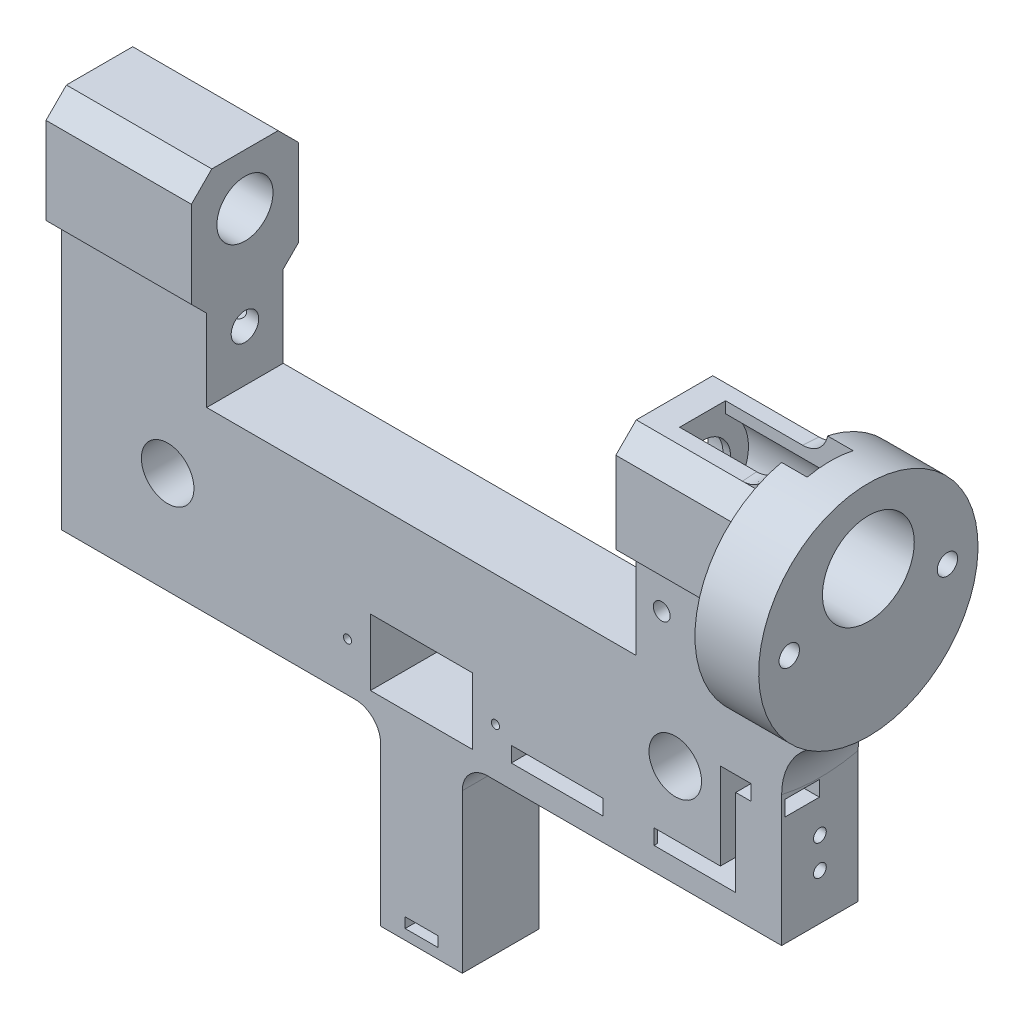
SolidWorks part; units mm, degrees
ref_plane "Front Plane" through (0, 0, 0) normal (0, 0, 1) x (1, 0, 0)
ref_plane "Top Plane" through (0, 0, 0) normal (0, 1, 0) x (1, 0, 0)
ref_plane "Right Plane" through (0, 0, 0) normal (1, 0, 0) x (0, 0, -1)
sketch "Croquis1" plane through (0, 0, 0) normal (0, 1, 0) x (1, 0, 0)
  line L1 (-20, -7.5) -> (20, -7.5)
  line L2 (-20, -7.5) -> (-20, 7.5)
  line L3 (-20, 7.5) -> (20, 7.5)
  line L4 (20, -7.5) -> (20, 7.5)
  line L5 (-20, -7.5) -> (20, 7.5) construction
  line L6 (-20, 7.5) -> (20, -7.5) construction
  point P0 (0, 0)
  dimension "D1" = 40
  dimension "D2" = 15
extrude "Saliente-Extruir1" add sketch "Croquis1" along normal blind 75
sketch "Croquis4" plane through (20, 0, 0) normal (1, 0, 0) x (0, 0, -1)
  line L5 (0, 75) -> (0, 46.5638) construction
  line L6 (-7.5, 75) -> (7.5, 75) construction
  line L11 (0, 58) -> (16.3781, 58) construction
  circle A0 centre (0, 58) radius 21.5
  circle A1 centre (0, 58) radius 15.5 construction
  circle A5 centre (-15.5, 58) radius 2
  circle A6 centre (15.5, 58) radius 2
  dimension "D3" = 43
  dimension "D5" = 31
  dimension "D1" = 4
  dimension "D2" = 4
  dimension "D4" = 17
extrude "Saliente-Extruir2" add sketch "Croquis4" against normal blind 3
sketch "Croquis7" plane through (0, 0, 7.5) normal (0, 0, 1) x (1, 0, 0)
  line L0 (20, 0) -> (-121.2, 0) construction
  line L1 (-121.2, 0) -> (-121.2, 75)
  line L2 (-121.2, 75) -> (-92.7, 75)
  line L3 (-92.7, 75) -> (-92.7, 35)
  line L4 (-92.7, 35) -> (-81.2, 35)
  line L5 (-81.2, 35) -> (-81.2, 0)
  line L6 (-81.2, 0) -> (-121.2, 0)
  line L7 (-81.2, 20) -> (-20, 20)
  line L8 (-81.2, 0) -> (-20, 0)
  line L9 (-59.6, 0) -> (-59.6, -30)
  line L10 (-41.6, 0) -> (-41.6, -30)
  line L11 (-59.6, -30) -> (-41.6, -30)
  line L12 (-20, 75) -> (-20, 0) construction
  line L13 (-50.6, 0) -> (-52.95, 0) construction
  line L14 (-99.5, 0) -> (-99.5, 20.0495) construction
  line L15 (20, 0) -> (-121.2, 0) construction
  line L16 (-50.6, 20) -> (-50.6, -48.6966) construction
  line M17 (-20, 75) -> (-20, 0)
  dimension "D1" = 141.2
  dimension "D2" = 75
  dimension "D3" = 28.5
  dimension "D4" = 11.5
  dimension "D5" = 35
  dimension "D6" = 9
  dimension "D7" = 30
  dimension "D8" = 68.6966
  dimension "D9" = 30
  dimension "D10" = 20
  dimension "D11" = 2.35
  dimension "D12" = 99.5
  dimension "D13" = 9
extrude "Saliente-Extruir3" add sketch "Croquis7" against normal blind 15 contours L9 L11 L10 L8 | L5 L8 L7 M17 | L6 L5 L4 L3 L2 L1 region at (-103.7807, 34.3307, 7.5) region at (-50.6, 10, 7.5) region at (-50.6, -15, 7.5)
sketch "Croquis8" plane through (0, 0, 7.5) normal (0, 0, 1) x (1, 0, 0)
  line L0 (-50.6, -30) -> (-50.6, 95.9893) construction
  line L1 (-59.6, -30) -> (-41.6, -30) construction
  line L2 (-41.6, 0) -> (20, 0) construction
  circle A6 centre (-0.85, 20) radius 2.7
  circle A7 centre (-100.35, 20) radius 2.7
  dimension "D1" = 5.4
  dimension "D2" = 20
  dimension "D3" = 49.75
extrude "Cortar-Extruir5" cut sketch "Croquis8" against normal blind 20
sketch "Croquis6" plane through (0, 0, 7.5) normal (0, 0, 1) x (1, 0, 0)
  line L0 (0, 75) -> (-8.5, 75) construction
  line L1 (-20, 75) -> (17, 75) construction
  line L2 (-20, 75) -> (-8.5, 75)
  line L3 (-8.5, 75) -> (-8.5, 35)
  line L4 (-8.5, 35) -> (-20, 35)
  line L5 (-20, 75) -> (-20, 20) construction
  line L6 (-20, 35) -> (-20, 75)
  line L7 (0, 25) -> (0, 75) construction
  dimension "D1" = 8.5
  dimension "D2" = 40
extrude "Cortar-Extruir4" cut sketch "Croquis6" against normal blind 40
extrude "Saliente-Extruir5" add sketch "Croquis4<2>" along normal blind 9.5
sketch "Croquis4<2>" plane through (20, 0, 0) normal (1, 0, 0) x (0, 0, -1) same geometry as "Croquis4"
sketch "Croquis3" plane through (-20, 0, 0) normal (-1, 0, 0) x (0, 0, 1)
  line L1 (-7.5, 0) -> (7.5, 0) construction
  line L2 (-7.5, 75) -> (7.5, 75) construction
  circle A0 centre (0, 65) radius 5.5
  circle A1 centre (0, 45) radius 2.7
  point P9 (0, 0)
  dimension "D1" = 11
  dimension "D3" = 5.4
  dimension "D2" = 10
  dimension "D4" = 20
  dimension "D5" = 45
extrude "Cortar-Extruir2" cut sketch "Croquis3" against normal mid plane 290
sketch "Croquis10" plane through (20, 0, 0) normal (1, 0, 0) x (0, 0, -1)
  circle A1 centre (0, 65) radius 7
  dimension "D2" = 14
extrude "Cortar-Extruir7" cut sketch "Croquis10" against normal blind 23
sketch "Croquis11" plane through (-121.2, 0, 0) normal (-1, 0, 0) x (0, 0, 1)
  circle A1 centre (0, 65) radius 6.6
  circle M2 centre (0, 65) radius 5.5
  dimension "D2" = 13.2
extrude "Cortar-Extruir8" cut sketch "Croquis11" against normal blind 6 contours A1 M2 region at (-121.2, 65, -6.4133)
sketch "Croquis13" plane through (-8.5, 0, 0) normal (-1, 0, 0) x (0, 0, 1)
  circle A0 centre (0, 65) radius 6.6
  dimension "D1" = 13.2
extrude "Cortar-Extruir10" cut sketch "Croquis13" against normal blind 4
sketch "Croquis17" plane through (0, 0, -7.5) normal (0, 0, -1) x (-1, 0, 0)
  line L0 (-17, 75) -> (8.5, 75) construction
  line L1 (8.5, 35) -> (8.5, 75) construction
  circle A0 centre (-3, 34) radius 0.8
  circle A1 centre (-3, 43.38) radius 0.8
  dimension "D4" = 1.6
  dimension "D5" = 1.6
  dimension "D1" = 9.38
  dimension "D2" = 41
  dimension "D3" = 11.5
extrude "Cortar-Extruir13" cut sketch "Croquis17" against normal blind 4 contours A0 | A1 region at (3, 34, -7.5) region at (3, 43.38, -7.5)
sketch "Croquis18" plane through (0, 0, -7.5) normal (0, 0, -1) x (-1, 0, 0)
  line L0 (20, 35) -> (81.2, 35)
  line L1 (81.2, 35) -> (81.2, 20)
  line L2 (81.2, 20) -> (20, 20)
  line L3 (20, 20) -> (20, 35)
extrude "Saliente-Extruir4" add sketch "Croquis18" against normal blind 15
sketch "Croquis19" plane through (0, 0, -7.5) normal (0, 0, -1) x (-1, 0, 0)
  line L0 (92.7, 35) -> (8.5, 35) construction
  circle A0 centre (28.5, 27) radius 0.8
  circle A1 centre (37.88, 27) radius 0.8
  dimension "D2" = 1.6
  dimension "D3" = 1.6
  dimension "D1" = 9.38
  dimension "D4" = 8
  dimension "D5" = 20
  dimension "D6" = 8
extrude "Cortar-Extruir14" cut sketch "Croquis19" against normal blind 5
sketch "Croquis20" plane through (0, 0, -7.5) normal (0, 0, -1) x (-1, 0, 0)
  line L0 (-20, 0) -> (41.6, 0) construction
  line L1 (40.6, 16) -> (60.6, 16)
  line L2 (40.6, 16) -> (40.6, 3)
  line L3 (40.6, 3) -> (60.6, 3)
  line L4 (60.6, 16) -> (60.6, 3)
  line L5 (40.6, 16) -> (60.6, 3) construction
  line L6 (40.6, 3) -> (60.6, 16) construction
  line L7 (92.7, 35) -> (8.5, 35) construction
  point P0 (50.6, 9.5)
  point P9 (50.6, 35)
  point P10 (50.6, 16)
  dimension "D1" = 20
  dimension "D2" = 13
  dimension "D3" = 3
extrude "Cortar-Extruir15" cut sketch "Croquis20" against normal blind 20
fillet "Redondeo7" radius 5 1 edges at (17, 75, 0)
sketch "Croquis15" plane through (0, 0, 7.5) normal (0, 0, 1) x (1, 0, 0)
  line L0 (-41.6, 0) -> (20, 0) construction
  line L1 (-8.5, 35) -> (-8.5, 75) construction
  circle A0 centre (-3.5, 45) radius 1.65
  dimension "D2" = 3.3
  dimension "D1" = 45
  dimension "D3" = 5
extrude "Cortar-Extruir11" cut sketch "Croquis15" against normal blind 9
extrude "Cortar-Extruir17" cut sketch "Croquis10<2>" along normal blind 35
sketch "Croquis10<2>" plane through (20, 0, 0) normal (1, 0, 0) x (0, 0, -1) same geometry as "Croquis10"
fillet "Redondeo8" radius 12 1 edges at (20, 36.5, 0)
sketch "Croquis22" plane through (0, 0, 7.5) normal (0, 0, 1) x (1, 0, 0)
  line L0 (-60.6, 3) -> (-60.6, 16) construction
  line L1 (-40.6, 3) -> (-60.6, 3) construction
  line L2 (-50.6, 16) -> (-50.6, -3.1342) construction
  line L3 (-60.6, 16) -> (-40.6, 16) construction
  circle A0 centre (-65.1, 9.5) radius 0.8
  circle A1 centre (-36.1, 9.5) radius 0.8
  dimension "D2" = 1.6
  dimension "D3" = 6.5
  dimension "D1" = 4.5
  dimension "D4" = 19.1342
  dimension "D5" = 270
extrude "Cortar-Extruir18" cut sketch "Croquis22" against normal blind 5
sketch "Croquis23" plane through (0, 0, -7.5) normal (0, 0, -1) x (-1, 0, 0)
  circle A1 centre (0.85, 20) radius 5.15
  circle A2 centre (100.35, 20) radius 5.15
  dimension "D2" = 10.3
  dimension "D3" = 10.3
extrude "Cortar-Extruir19" cut sketch "Croquis23" against normal blind 40
sketch "Croquis24" plane through (29.5, 0, 0) normal (1, 0, 0) x (0, 0, -1)
  circle A0 centre (0, 45) radius 2.75
extrude "Saliente-Extruir6" add sketch "Croquis24" against normal blind 26.5
sketch "Croquis25" plane through (0, 75, 0) normal (0, 1, 0) x (1, 0, 0)
  line L0 (-3, -4.5) -> (-3, 4.5)
  line L1 (-3, 4.5) -> (22, 4.5)
  line L2 (22, 4.5) -> (22, -4.5)
  line L3 (22, -4.5) -> (-3, -4.5)
  line L4 (-8.5, -7.5) -> (12.3137, -7.5) construction
  line L5 (12.3137, 7.5) -> (-8.5, 7.5) construction
  line L6 (-8.5, 7.5) -> (-8.5, -7.5) construction
  dimension "D1" = 3
  dimension "D2" = 3
  dimension "D3" = 5.5
  dimension "D4" = 25
extrude "Cortar-Extruir20" cut sketch "Croquis25" against normal blind 10
extrude "Cortar-Extruir21" cut sketch "Croquis25<2>" along normal blind 10 contours L3 L1 L0 | L3 L2 L1 region at (9.5, 75, 0)
sketch "Croquis25<2>" plane through (0, 75, 0) normal (0, 1, 0) x (1, 0, 0) same geometry as "Croquis25"
sketch "Croquis26" plane through (0, 0, 7.5) normal (0, 0, 1) x (1, 0, 0)
  line L0 (-59.6, -30) -> (-59.6, 0)
  line L1 (-121.2, 0) -> (-59.6, 0) construction
  line L2 (-59.6, 0) -> (-58.6, 0)
  line L3 (-58.6, 0) -> (-58.6, -30)
  line L4 (-59.6, -30) -> (-41.6, -30) construction
  line L5 (-58.6, -30) -> (-59.6, -30)
  line L6 (-41.6, -30) -> (-42.6, -30)
  line L7 (-42.6, -30) -> (-42.6, 0)
  line L8 (-42.6, 0) -> (-41.6, 0)
  line L9 (-41.6, 0) -> (-41.6, -30)
  dimension "D1" = 1
  dimension "D2" = 1
extrude "Cortar-Extruir22" cut sketch "Croquis26" against normal blind 30
fillet "Redondeo9" radius 5 1 edges at (-58.6, 0, 0)
fillet "Redondeo10" radius 5 1 edges at (-42.6, 0, 0)
sketch "Croquis28" plane through (20, 0, 0) normal (1, 0, 0) x (0, 0, -1)
  line L0 (-7.5, 0) -> (7.5, 0) construction
  line L1 (-7.5, 25.6206) -> (-7.5, 0) construction
  circle A0 centre (0, 15) radius 1.25
  circle A1 centre (0, 9) radius 1.25
  dimension "D1" = 2.5
  dimension "D4" = 2.5
  dimension "D2" = 15
  dimension "D3" = 7.5
  dimension "D5" = 6
  dimension "D6" = 9
extrude "Cortar-Extruir23" cut sketch "Croquis28" against normal blind 7.4
sketch "Croquis29" plane through (0, 0, -7.5) normal (0, 0, -1) x (-1, 0, 0)
  line L0 (-20, 0) -> (37.6, 0) construction
  line L1 (-20, 25.6206) -> (-20, 0) construction
  circle A0 centre (31, 6) radius 1.5
  circle A1 centre (25, 6) radius 1.5
  dimension "D3" = 3
  dimension "D4" = 3
  dimension "D1" = 6
  dimension "D2" = 6
  dimension "D5" = 45
  dimension "D6" = 6
extrude "Cortar-Extruir24" cut sketch "Croquis29" against normal blind 47.4
sketch "Croquis30" plane through (0, 0, 7.5) normal (0, 0, 1) x (1, 0, 0)
  line L0 (20, 4.5) -> (20, 7.5)
  line L1 (20, 4.5) -> (-33, 4.5)
  line L2 (20, 7.5) -> (-33, 7.5)
  line L3 (-33, 4.5) -> (-33, 7.5)
  line L4 (20, 4.5) -> (-33, 7.5) construction
  line L5 (20, 7.5) -> (-33, 4.5) construction
  line L6 (20, 25.6206) -> (20, 0) construction
  line L7 (-37.6, 0) -> (20, 0) construction
  line L8 (-25, 7.5) -> (-25, 4.5) construction
  line L9 (-25, 7.5) -> (-25, 4.5)
  line L10 (8, 7.5) -> (8, 24.5)
  line L11 (8, 24.5) -> (20, 24.5)
  line L12 (20, 24.5) -> (20, 21.5)
  line L13 (20, 21.5) -> (11, 21.5)
  line L14 (11, 21.5) -> (11, 7.5)
  line L15 (11, 7.5) -> (11, 4.5)
  circle A0 centre (-31, 6) radius 1.5 construction
  circle A2 centre (-25, 6) radius 1.5 construction
  point P1 (-6.5, 6)
  circle M5 centre (-31, 6) radius 1.5
  circle M6 centre (-25, 6) radius 1.5
  line M23 (20, 0) -> (20, 25.6206)
  dimension "D1" = 2
  dimension "D2" = 3
  dimension "D3" = 0
  dimension "D4" = 6
  dimension "D5" = 3
  dimension "D6" = 3
  dimension "D7" = 17
  dimension "D8" = 9
extrude "Cortar-Extruir25" cut sketch "Croquis30" against normal blind 4.4 contours L3 L1 L2 M5 | L2 L1 M6 M5 region at (-28, 6, 7.5) region at (-32.5209, 6, 7.5)
extrude "Cortar-Extruir26" cut sketch "Croquis30<3>" against normal blind 7.4 contours L2 L1 M23 M6 region at (-6.4126, 6, 7.5)
sketch "Croquis30<3>" plane through (0, 0, 7.5) normal (0, 0, 1) x (1, 0, 0) same geometry as "Croquis30"
extrude "Cortar-Extruir27" cut sketch "Croquis30<4>" against normal blind 7.4 contours L14 L13 L11 L10 L2 M23 region at (9.5, 7.7081, 7.5)
sketch "Croquis30<4>" plane through (0, 0, 7.5) normal (0, 0, 1) x (1, 0, 0) same geometry as "Croquis30"
sketch "Croquis32" plane through (-121.2, 0, 0) normal (-1, 0, 0) x (0, 0, 1)
  line L0 (-7.5, 75) -> (-10.5, 75)
  line L1 (-10.5, 75) -> (-10.5, 55)
  line L2 (-7.5, 55) -> (-7.5, 75)
  line L3 (-7.5, 0) -> (-7.5, 75) construction
  line L4 (7.5, 75) -> (10.5, 75)
  line L5 (10.5, 75) -> (10.5, 55)
  line L6 (10.5, 55) -> (7.5, 55)
  line L7 (7.5, 0) -> (7.5, 75) construction
  line L8 (7.5, 55) -> (7.5, 75)
  line L9 (-10.5, 55) -> (-7.5, 55)
  dimension "D1" = 3
  dimension "D2" = 3
  dimension "D3" = 20
  dimension "D4" = 20
extrude "Saliente-Extruir8" add sketch "Croquis32" against normal blind 28.5
sketch "Croquis33" plane through (-8.5, 0, 0) normal (-1, 0, 0) x (0, 0, 1)
  line L0 (-7.5, 75) -> (-7.5, 55)
  line L2 (-7.5, 55) -> (-11.5, 55)
  line L3 (-11.5, 55) -> (-11.5, 75)
  line L4 (-11.5, 75) -> (-7.5, 75)
  line L5 (7.5, 75) -> (11.5, 75)
  line L6 (11.5, 75) -> (11.5, 55)
  line L7 (11.5, 55) -> (7.5, 55)
  line L9 (7.5, 55) -> (7.5, 75)
  dimension "D1" = 4
  dimension "D2" = 4
  dimension "D3" = 20
  dimension "D4" = 20
extrude "Saliente-Extruir9" add sketch "Croquis33" against normal blind 28.5
sketch "Croquis34" plane through (0, 0, 7.5) normal (0, 0, 1) x (1, 0, 0)
  line L0 (20, 21.5) -> (14, 21.5)
  line L1 (20, 21.5) -> (11, 21.5) construction
  line L2 (14, 21.5) -> (14, 24.5)
  line L3 (8, 24.5) -> (20, 24.5) construction
  line L4 (14, 24.5) -> (20, 24.5)
  line L5 (20, 25.6206) -> (20, 24.5) construction
  line L6 (20, 24.5) -> (20, 21.5)
  line L7 (-15, 7.5) -> (-15, 4.5)
  line L8 (8, 7.5) -> (-33, 7.5) construction
  line L9 (11, 4.5) -> (-33, 4.5) construction
  line L10 (-15, 4.5) -> (-5, 4.5)
  line L11 (-5, 4.5) -> (-5, 7.5)
  line L12 (-5, 7.5) -> (-15, 7.5)
  line L13 (-33, 4.5) -> (-33, 7.5) construction
  dimension "D1" = 6
  dimension "D2" = 10
  dimension "D3" = 18
extrude "Saliente-Extruir10" add sketch "Croquis34" against normal blind 0.7
sketch "Croquis35" plane through (29.5, 0, 0) normal (1, 0, 0) x (0, 0, -1)
  circle A0 centre (0, 65) radius 9
  dimension "D1" = 18
extrude "Cortar-Extruir28" cut sketch "Croquis35" against normal blind 32.5
sketch "Croquis36" plane through (0, 0, -10.5) normal (0, 0, -1) x (-1, 0, 0)
  line L1 (92.7, 75) -> (92.7, 55) construction
  line L2 (92.7, 35) -> (8.5, 35) construction
  circle A0 centre (96.7, 45) radius 1.65
  dimension "D3" = 3.3
  dimension "D1" = 10
  dimension "D2" = 4
extrude "Cortar-Extruir29" cut sketch "Croquis36" against normal blind 12.5
chamfer "Chaflán2" distance 4 angle 45 4 edges at (-106.95, 75, 10.5) (-106.95, 75, -10.5) (4.25, 75, 11.5) (4.25, 75, -11.5)
chamfer "Chaflán3" distance 4 angle 45 1 edges at (-106.95, 55, -7.5)
chamfer "Chaflán4" distance 4 angle 45 3 edges at (4.25, 55, 7.5) (-106.95, 55, 7.5) (4.25, 55, -7.5)
sketch "Croquis37" plane through (0, -30, 0) normal (0, -1, 0) x (1, 0, 0)
  line L0 (-58.6, -7.5) -> (-58.6, 7.5)
  line L1 (-58.6, -7.5) -> (-42.6, -7.5)
  line L2 (-58.6, 7.5) -> (-42.6, 7.5)
  line L3 (-42.6, -7.5) -> (-42.6, 7.5)
  line L4 (-58.6, -7.5) -> (-42.6, 7.5) construction
  line L5 (-58.6, 7.5) -> (-42.6, -7.5) construction
  line L6 (-58.6, -7.5) -> (-58.6, 7.5) construction
  line L7 (-58.6, 7.5) -> (-42.6, 7.5) construction
  point P1 (-50.6, 0)
  point P2 (-50.6, 7.5)
  point P9 (-58.6, 0)
  point P12 (-50.6, 7.5)
  dimension "D1" = 16
  dimension "D2" = 15
extrude "Saliente-Extruir11" add sketch "Croquis37" along normal blind 6
sketch "Croquis38" plane through (0, 0, 7.5) normal (0, 0, 1) x (1, 0, 0)
  line L0 (-50.6, -36) -> (-50.6, -29.1762) construction
  line L1 (-42.6, -36) -> (-58.6, -36) construction
  line L2 (-47.4, -34) -> (-47.4, -32)
  line L3 (-47.4, -34) -> (-53.8, -34)
  line L4 (-47.4, -32) -> (-53.8, -32)
  line L5 (-53.8, -34) -> (-53.8, -32)
  line L6 (-47.4, -34) -> (-53.8, -32) construction
  line L7 (-47.4, -32) -> (-53.8, -34) construction
  point P5 (-50.6, -33)
  dimension "D1" = 2
  dimension "D2" = 6.4
  dimension "D3" = 3
  dimension "D4" = 2
extrude "Cortar-Extruir30" cut sketch "Croquis38" against normal blind 6
sketch "Croquis39" plane through (0, -36, 0) normal (0, -1, 0) x (1, 0, 0)
  line L0 (-50.6, 7.5) -> (-50.6, 3.4566) construction
  line L1 (-42.6, 7.5) -> (-58.6, 7.5) construction
  line L2 (-47.4, 3.9) -> (-47.4, 1.5)
  line L3 (-47.4, 3.9) -> (-53.8, 3.9)
  line L4 (-47.4, 1.5) -> (-53.8, 1.5)
  line L5 (-53.8, 3.9) -> (-53.8, 1.5)
  line L6 (-47.4, 3.9) -> (-53.8, 1.5) construction
  line L7 (-47.4, 1.5) -> (-53.8, 3.9) construction
  line L8 (-42.6, -7.5) -> (-42.6, 7.5) construction
  point P4 (-50.6, 1.5)
  point P5 (-50.6, 2.7)
  dimension "D1" = 6.4
  dimension "D2" = 6
  dimension "D3" = 2.4
  dimension "D4" = 4.8
extrude "Cortar-Extruir31" cut sketch "Croquis39" against normal blind 4
chamfer "Chaflán5" distance 1 angle 45 1 edges at (-50.6, -34, 3.9)
mirror "Simetría1" about plane through (0, 0, 0) normal (0, 0, 1) of "Cortar-Extruir31", "Chaflán5", "Cortar-Extruir30"
